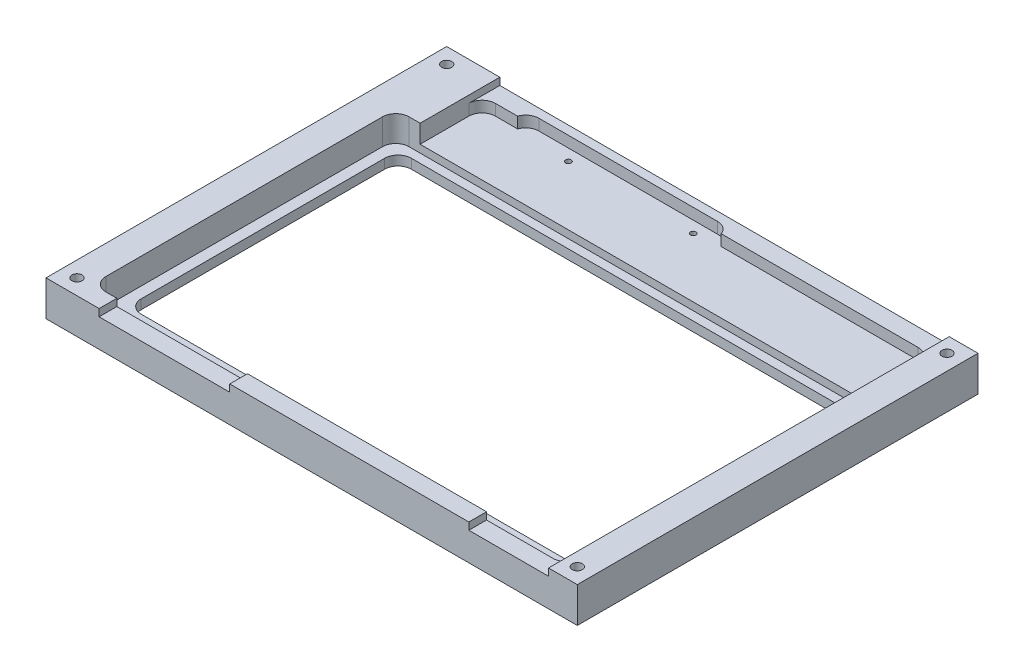
SolidWorks part; units mm, degrees
ref_plane "前视基准面" through (0, 0, 0) normal (0, 0, 1) x (1, 0, 0)
ref_plane "上视基准面" through (0, 0, 0) normal (0, 1, 0) x (1, 0, 0)
ref_plane "右视基准面" through (0, 0, 0) normal (1, 0, 0) x (0, 0, -1)
sketch "草图1" plane through (0, 0, 0) normal (0, 1, 0) x (1, 0, 0)
  line L0 (57, 45.25) -> (60, 45.25)
  line L1 (-57, -45.25) -> (57, -45.25)
  line L2 (-60, -42.25) -> (-60, 42.25)
  line L3 (-57, 45.25) -> (57, 45.25)
  line L4 (60, -42.25) -> (60, 42.25)
  line L5 (-60, -45.25) -> (60, 45.25) construction
  line L6 (-60, 45.25) -> (60, -45.25) construction
  line L7 (60, -42.25) -> (60, -45.25)
  line L8 (60, -45.25) -> (57, -45.25)
  line L9 (-57, -45.25) -> (-60, -45.25)
  line L10 (-60, -45.25) -> (-60, -42.25)
  line L11 (-57, 45.25) -> (-60, 45.25)
  line L12 (-60, 45.25) -> (-60, 42.25)
  line L13 (60, 42.25) -> (60, 45.25)
  point P0 (0, 0)
  dimension "D1" = 90.5
  dimension "D2" = 120
extrude "凸台-拉伸1" add sketch "草图1" along normal blind 8
sketch "草图2" plane through (0, 8, 0) normal (0, 1, 0) x (1, 0, 0)
  line L0 (-53, 45.25) -> (-53, -45.25) construction
  line L1 (60, 45.25) -> (-60, 45.25) construction
  line L2 (-60, -45.25) -> (60, -45.25) construction
  line L3 (53.5, 45.25) -> (53.5, -45.25) construction
  line L4 (-60, 45.25) -> (-60, -45.25) construction
  line L6 (60, -45.25) -> (60, 45.25) construction
  line L7 (53.5, -41.25) -> (-53.5, -41.25)
  line L8 (53.5, -41.25) -> (53.5, 27.25)
  line L9 (53.5, 27.25) -> (-53.5, 27.25)
  line L10 (-53.5, -41.25) -> (-53.5, 27.25)
  line L11 (53.5, -41.25) -> (-53.5, 27.25) construction
  line L12 (53.5, 27.25) -> (-53.5, -41.25) construction
  line L17 (-51, 25.25) -> (51, 25.25)
  line L18 (-51, 25.25) -> (-51, -35.75)
  line L19 (-51, -35.75) -> (51, -35.75)
  line L20 (51, 25.25) -> (51, -35.75)
  line L25 (-48, 45.25) -> (53.5, 45.25)
  line L26 (-48, 45.25) -> (-48, -45.25)
  line L27 (-48, -45.25) -> (53.5, -45.25)
  line L28 (53.5, 45.25) -> (53.5, -45.25)
  line L29 (53.5, 40.636) -> (-48, 40.636) construction
  line L30 (35.5, -45.25) -> (-18.5, -45.25)
  line L31 (35.5, -45.25) -> (35.5, -41.25)
  line L32 (35.5, -41.25) -> (-18.5, -41.25)
  line L33 (-18.5, -45.25) -> (-18.5, -41.25)
  circle A0 centre (0.295, 40.636) radius 0.625
  circle A1 centre (-27.9, 40.636) radius 0.625
  point P12 (0, -7)
  point P17 (0, -7)
  dimension "D2" = 1.25
  dimension "D11" = 1.25
  dimension "D1" = 7
  dimension "D3" = 107
  dimension "D4" = 68.5
  dimension "D5" = 4
  dimension "D6" = 2.5
  dimension "D7" = 2.5
  dimension "D8" = 5.5
  dimension "D9" = 2
  dimension "D10" = 28.195
  dimension "D12" = 59.705
  dimension "D13" = 101.5
  dimension "D14" = 9.228
  dimension "D15" = 54
  dimension "D16" = 18
extrude "PCB整体下沉" cut sketch "草图2" against normal blind 1.62 contours L26 L27 L28 L25
extrude "屏显示" cut sketch "草图2<4>" against normal up to next contours L19 L20 L17 L18
sketch "草图2<4>" plane through (0, 8, 0) normal (0, 1, 0) x (1, 0, 0) same geometry as "草图2"
extrude "屏外框" cut sketch "草图2<5>" against normal blind 5.85 contours L9 L10 L7 L8
sketch "草图2<5>" plane through (0, 8, 0) normal (0, 1, 0) x (1, 0, 0) same geometry as "草图2"
sketch "草图3" plane through (0, 6.38, 0) normal (0, 1, 0) x (1, 0, 0)
  line L0 (-48, 45.25) -> (-48, 27.25) construction
  line L1 (-48, 41.25) -> (53.5, 41.25)
  line L2 (-48, 41.25) -> (-48, 27.25)
  line L3 (-48, 27.25) -> (53.5, 27.25)
  line L4 (53.5, 41.25) -> (53.5, 27.25)
  line L5 (-48, 45.25) -> (53.5, 45.25) construction
  line L12 (-40, 27.25) -> (6, 27.25)
  line L13 (-40, 27.25) -> (-40, 43.25)
  line L14 (-40, 43.25) -> (6, 43.25)
  line L15 (6, 27.25) -> (6, 43.25)
  dimension "D1" = 4
  dimension "D2" = 2
  dimension "D3" = 8
  dimension "D4" = 54
extrude "穿孔焊盘切除" cut sketch "草图3" against normal blind 2.5 contours L1 L4 L3 L2
extrude "穿孔焊盘切除2" cut sketch "草图3<3>" against normal blind 2.5 contours L1 L15 L14 L13 region at (-17, 6.38, -42.25)
sketch "草图3<3>" plane through (0, 6.38, 0) normal (0, 1, 0) x (1, 0, 0) same geometry as "草图3"
sketch "四周螺孔" plane through (0, 0, 0) normal (0, 1, 0) x (1, 0, 0)
  line L0 (-60, 41.75) -> (60, 41.75) construction
  line L1 (-60, 45.25) -> (-60, -45.25) construction
  line L2 (60, -45.25) -> (60, 45.25) construction
  line L3 (-60, -41.75) -> (60, -41.75) construction
  line L4 (-56.5, 45.25) -> (-56.5, -45.25) construction
  line L5 (-48, 45.25) -> (-60, 45.25) construction
  line L6 (-60, -45.25) -> (-48, -45.25) construction
  line L7 (56.5, 45.25) -> (56.5, -45.25) construction
  line L10 (60, 45.25) -> (53.5, 45.25) construction
  line L11 (53.5, -45.25) -> (60, -45.25) construction
  circle A0 centre (-56.5, -41.75) radius 2.15
  circle A1 centre (-56.5, -41.75) radius 1.15
  circle A2 centre (-56.5, 41.75) radius 2.15
  circle A3 centre (-56.5, 41.75) radius 1.15
  circle A4 centre (56.5, 41.75) radius 2.15
  circle A5 centre (56.5, 41.75) radius 1.15
  circle A6 centre (56.5, -41.75) radius 2.15
  circle A7 centre (56.5, -41.75) radius 1.15
  point P20 (-56.5, -41.75)
  point P21 (56.5, -41.75)
  point P22 (56.5, 41.75)
  point P23 (-56.5, 41.75)
  dimension "D5" = 4.3
  dimension "D7" = 4.3
  dimension "D9" = 4.3
  dimension "D11" = 4.3
  dimension "D6" = 2.3
  dimension "D8" = 2.3
  dimension "D10" = 2.3
  dimension "D12" = 2.3
  dimension "D1" = 3.5
  dimension "D2" = 3.5
  dimension "D3" = 3.5
  dimension "D4" = 3.5
extrude "杯头沉孔" cut sketch "四周螺孔" along normal blind 2.2 contours A2 | A0 | A4 | A6
extrude "螺纹通孔" cut sketch "四周螺孔<3>" along normal through all contours A1 | A3 | A5 | A7
sketch "四周螺孔<3>" plane through (0, 0, 0) normal (0, 1, 0) x (1, 0, 0) same geometry as "四周螺孔"
fillet "圆角1" radius 3 12 edges at (-51, 1.075, -25.25) (-53.5, 5.075, -27.25) (-51, 1.075, 35.75) (-53.5, 5.075, 41.25) (51, 1.075, 35.75) (53.5, 4.265, 41.25) (51, 1.075, -25.25) (53.5, 3.015, -27.25) (6, 5.13, -43.25) (-40, 5.13, -43.25) (-48, 5.13, -41.25) (53.5, 5.13, -41.25)
extrude "LED孔" cut sketch "草图2<6>" against normal through all contours A0 | A1
sketch "草图2<6>" plane through (0, 8, 0) normal (0, 1, 0) x (1, 0, 0) same geometry as "草图2"
extrude "PCB开槽档边" add sketch "草图2<7>" along normal blind 1.62 from surface contours L33 L27 L31 L7 region at (8.5, 8, 43.25) starting at face at (12.4243, 6.38, 42.3743)
sketch "草图2<7>" plane through (0, 8, 0) normal (0, 1, 0) x (1, 0, 0) same geometry as "草图2"
equation "\"杯头\"= 4.3mm"
equation "\"底孔\"= 1.6mm"
equation "\"让刀\" = 3mm"
equation "\"D5@四周螺孔\"=\"杯头\""
equation "\"D7@四周螺孔\"=\"杯头\""
equation "\"D9@四周螺孔\"=\"杯头\""
equation "\"D11@四周螺孔\"=\"杯头\""
equation "\"通孔\"= 2.3mm"
equation "\"D6@四周螺孔\"=\"通孔\""
equation "\"D8@四周螺孔\"=\"通孔\""
equation "\"D10@四周螺孔\"=\"通孔\""
equation "\"D12@四周螺孔\"=\"通孔\""
